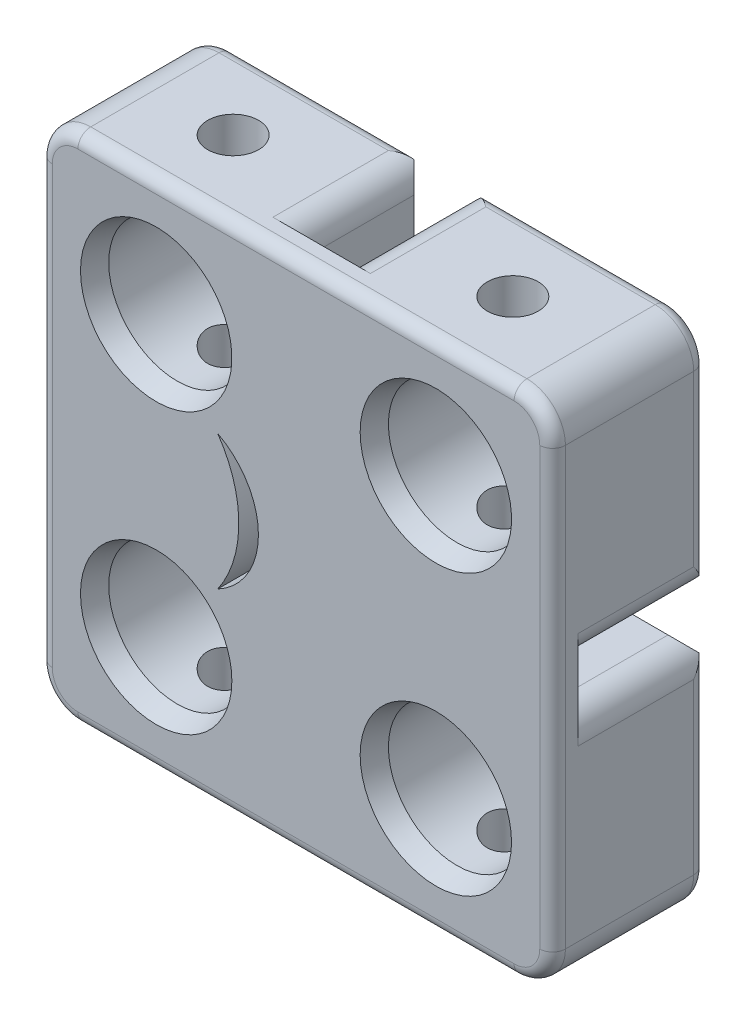
SolidWorks part; units mm, degrees
ref_plane "Front Plane" through (0, 0, 0) normal (0, 0, 1) x (1, 0, 0)
ref_plane "Top Plane" through (0, 0, 0) normal (0, 1, 0) x (1, 0, 0)
ref_plane "Right Plane" through (0, 0, 0) normal (1, 0, 0) x (0, 0, -1)
sketch "Sketch1" plane through (0, 0, 0) normal (0, 0, 1) x (1, 0, 0)
  line L1 (0, 0) -> (50.8, 0)
  line L2 (0, 0) -> (0, 50.8)
  line L3 (0, 50.8) -> (50.8, 50.8)
  line L4 (50.8, 0) -> (50.8, 50.8)
  dimension "D1" = 50.8
extrude "Boss-Extrude1" add sketch "Sketch1" along normal blind 15.24
sketch "Sketch2" plane through (0, 0, 0) normal (0, 0, -1) x (-1, 0, 0)
  line L0 (-50.8, 50.8) -> (0, 50.8) construction
  line L1 (-27.686, 50.8) -> (-23.114, 50.8)
  line L2 (-27.686, 50.8) -> (-27.686, 27.686)
  line L3 (-27.686, 0) -> (-23.114, 0)
  line L4 (-23.114, 50.8) -> (-23.114, 27.686)
  line L5 (0, 0) -> (-50.8, 0) construction
  line L6 (-23.114, 23.114) -> (-23.114, 0)
  line L7 (-50.8, 27.686) -> (-27.686, 27.686)
  line L8 (-50.8, 27.686) -> (-50.8, 23.114)
  line L9 (-50.8, 23.114) -> (-27.686, 23.114)
  line L10 (0, 27.686) -> (0, 23.114)
  line L11 (-23.114, 23.114) -> (0, 23.114)
  line L12 (-23.114, 27.686) -> (0, 27.686)
  line L13 (-50.8, 0) -> (-50.8, 50.8) construction
  line L14 (0, 50.8) -> (0, 0) construction
  line L15 (-27.686, 23.114) -> (-27.686, 0)
  point P12 (0, 25.4)
  point P19 (-25.4, 50.8)
  dimension "D1" = 4.572
extrude "Cut-Extrude1" cut sketch "Sketch2" against normal blind 12.7
sketch "Sketch3" plane through (0, 50.8, 0) normal (0, 1, 0) x (1, 0, 0)
  line L0 (11.557, 0) -> (11.557, -15.24) construction
  line L1 (23.114, 0) -> (0, 0) construction
  line L2 (50.8, -15.24) -> (0, -15.24) construction
  line L3 (39.243, 0) -> (39.243, -15.24) construction
  line L4 (50.8, 0) -> (27.686, 0) construction
  circle A0 centre (11.557, -7.62) radius 2.5217
  circle A1 centre (39.243, -7.62) radius 2.5217
  dimension "D1" = 5.0434
extrude "Cut-Extrude2" cut sketch "Sketch3" against normal through all
sketch "Sketch4" plane through (0, 0, 0) normal (0, 0, -1) x (-1, 0, 0)
  line L0 (-27.686, 39.243) -> (-50.8, 39.243) construction
  line L1 (-27.686, 50.8) -> (-27.686, 27.686) construction
  line L2 (-50.8, 27.686) -> (-50.8, 50.8) construction
  line L3 (-50.8, 11.557) -> (-27.686, 11.557) construction
  line L6 (-50.8, 0) -> (-50.8, 23.114) construction
  line L9 (-27.686, 23.114) -> (-27.686, 0) construction
  line L10 (-11.557, 50.8) -> (-11.557, 27.686) construction
  line L11 (-23.114, 50.8) -> (0, 50.8) construction
  line L12 (0, 27.686) -> (-23.114, 27.686) construction
  circle A0 centre (-39.243, 39.243) radius 6.7733
  circle A1 centre (-11.557, 39.243) radius 6.7733
  circle A2 centre (-11.557, 11.557) radius 6.7733
  circle A3 centre (-39.243, 11.557) radius 6.7733
  point P9 (-39.243, 39.243)
  dimension "D1" = 13.5467
  dimension "D2" = 2
  dimension "D3" = 2
extrude "Cut-Extrude3" cut sketch "Sketch4" against normal through all
sketch "Sketch5" plane through (0, 0, 0) normal (0, 0, -1) x (-1, 0, 0)
  line L0 (-25.4, 32.5842) -> (-32.5842, 25.4)
  line L2 (-32.5842, 25.4) -> (-25.4, 18.2158)
  line L4 (-25.4, 18.2158) -> (-18.2158, 25.4)
  line L5 (-18.2158, 25.4) -> (-25.4, 32.5842)
  line L7 (-25.4, 50.8) -> (-25.4, 0) construction
  line L8 (-23.114, 50.8) -> (-27.686, 50.8) construction
  line L9 (-27.686, 0) -> (-23.114, 0) construction
  line L10 (-50.8, 25.4) -> (0, 25.4) construction
  line L11 (-50.8, 27.686) -> (-50.8, 23.114) construction
  line L12 (0, 23.114) -> (0, 27.686) construction
  dimension "D1" = 10.16
extrude "Cut-Extrude4" cut sketch "Sketch5" against normal blind 12.7
sketch "Sketch6" plane through (0, 0, 15.24) normal (0, 0, 1) x (1, 0, 0)
  line L0 (25.4, 50.8) -> (25.4, 0) construction
  line L1 (50.8, 50.8) -> (0, 50.8) construction
  line L2 (0, 25.4) -> (50.8, 25.4) construction
  line L3 (0, 50.8) -> (0, 0) construction
  line L4 (50.8, 0) -> (50.8, 50.8) construction
  line L5 (0, 0) -> (50.8, 0) construction
  line L6 (50.8, 25.4) -> (0, 25.4) construction
  arc A6 (17.6438, 32.0723) -> (17.6438, 18.7277) centre (8.0569, 25.4) cw
  arc A7 (17.6438, 32.0723) -> (17.6438, 18.7277) centre (14.1431, 25.4) cw
extrude "Cut-Extrude7" cut sketch "Sketch6" against normal through all
ref_plane "Plane1" through (11.557, 0, 0) normal (1, 0, 0) x (0, 0, -1)
ref_plane "Plane2" through (39.243, 0, 0) normal (-1, 0, 0) x (0, 0, 1)
sketch "Sketch10" plane through (11.557, 0, 0) normal (1, 0, 0) x (0, 0, -1)
  line L0 (0, 39.243) -> (-15.24, 39.243) construction
  line L1 (0, 50.8) -> (0, 27.686) construction
  line L2 (-15.24, 50.8) -> (-15.24, 0) construction
  line L3 (-15.24, 45.593) -> (-11.938, 45.593)
  line L5 (-15.24, 0) -> (-15.24, 50.8) construction
  line L6 (-11.938, 45.593) -> (-15.24, 46.736)
  line L7 (-15.24, 46.736) -> (-15.24, 45.593)
  dimension "D1" = 12.7
  dimension "D2" = 14.986
  dimension "D3" = 3.302
revolve "Cut-Revolve1" cut sketch "Sketch10" angle 360 about L0
sketch "Sketch13" plane through (11.557, 0, 0) normal (1, 0, 0) x (0, 0, -1)
  line L0 (0, 11.557) -> (-15.24, 11.557) construction
  line L1 (0, 0) -> (0, 23.114) construction
  line L2 (-15.24, 0) -> (-15.24, 50.8) construction
  line L3 (-15.24, 17.907) -> (-11.938, 17.907)
  line L4 (-11.938, 17.907) -> (-15.24, 19.05)
  line L5 (-15.24, 19.05) -> (-15.24, 17.907)
  dimension "D1" = 12.7
  dimension "D2" = 14.986
  dimension "D3" = 3.302
revolve "Cut-Revolve2" cut sketch "Sketch13" angle 360 about L0
sketch "Sketch14" plane through (39.243, 0, 0) normal (-1, 0, 0) x (0, 0, 1)
  line L0 (0, 39.243) -> (15.24, 39.243) construction
  line L1 (0, 50.8) -> (0, 27.686) construction
  line L2 (15.24, 50.8) -> (15.24, 0) construction
  line L3 (11.938, 45.593) -> (15.24, 45.593)
  line L4 (15.24, 45.593) -> (15.24, 46.736)
  line L5 (15.24, 46.736) -> (11.938, 45.593)
  dimension "D1" = 14.986
  dimension "D2" = 12.7
  dimension "D3" = 3.302
revolve "Cut-Revolve3" cut sketch "Sketch14" angle 360 about L0
sketch "Sketch15" plane through (39.243, 0, 0) normal (-1, 0, 0) x (0, 0, 1)
  line L0 (0, 11.557) -> (15.24, 11.557) construction
  line L1 (0, 23.114) -> (0, 0) construction
  line L2 (15.24, 50.8) -> (15.24, 0) construction
  line L3 (15.24, 17.907) -> (11.938, 17.907)
  line L4 (11.938, 17.907) -> (15.24, 19.05)
  line L5 (15.24, 19.05) -> (15.24, 17.907)
  dimension "D1" = 12.7
  dimension "D2" = 14.986
  dimension "D3" = 3.302
revolve "Cut-Revolve4" cut sketch "Sketch15" angle 360 about L0
chamfer "Chamfer1" distance 1.27 angle 45 12 edges at (40.5491, 23.114, 0) (27.686, 10.2509, 0) (28.9921, 21.8079, 0) (40.5491, 27.686, 0) (27.686, 40.5491, 0) (28.9921, 28.9921, 0) (23.114, 40.5491, 0) (22.1084, 29.2926, 0) (23.114, 10.2509, 0) (22.1084, 21.5074, 0) (9.7556, 27.686, 0) (9.7556, 23.114, 0)
fillet "Fillet1" [suppressed] radius 0.254
fillet "Fillet2" radius 1.27 12 edges at (10.922, 0, 0) (0, 10.922, 0) (0, 39.878, 0) (10.922, 50.8, 0) (39.878, 50.8, 0) (50.8, 39.878, 0) (39.878, 0, 0) (50.8, 10.922, 0) (0, 25.4, 15.24) (50.8, 25.4, 15.24) (25.4, 0, 15.24) (25.4, 50.8, 15.24)
fillet "Fillet3" radius 3.81 12 edges at (0.372, 0.372, 14.868) (0.372, 0.372, 0.372) (0.372, 50.428, 14.868) (0.372, 50.428, 0.372) (50.428, 50.428, 14.868) (50.428, 50.428, 0.372) (50.428, 0.372, 14.868) (50.428, 0.372, 0.372) (0, 0, 7.62) (0, 50.8, 7.62) (50.8, 50.8, 7.62) (50.8, 0, 7.62)
fillet "Fillet4" radius 2.54 8 edges at (0, 23.114, 6.985) (0, 27.686, 6.985) (23.114, 50.8, 6.985) (50.8, 23.114, 6.985) (50.8, 27.686, 6.985) (27.686, 50.8, 6.985) (27.686, 0, 6.985) (23.114, 0, 6.985)
